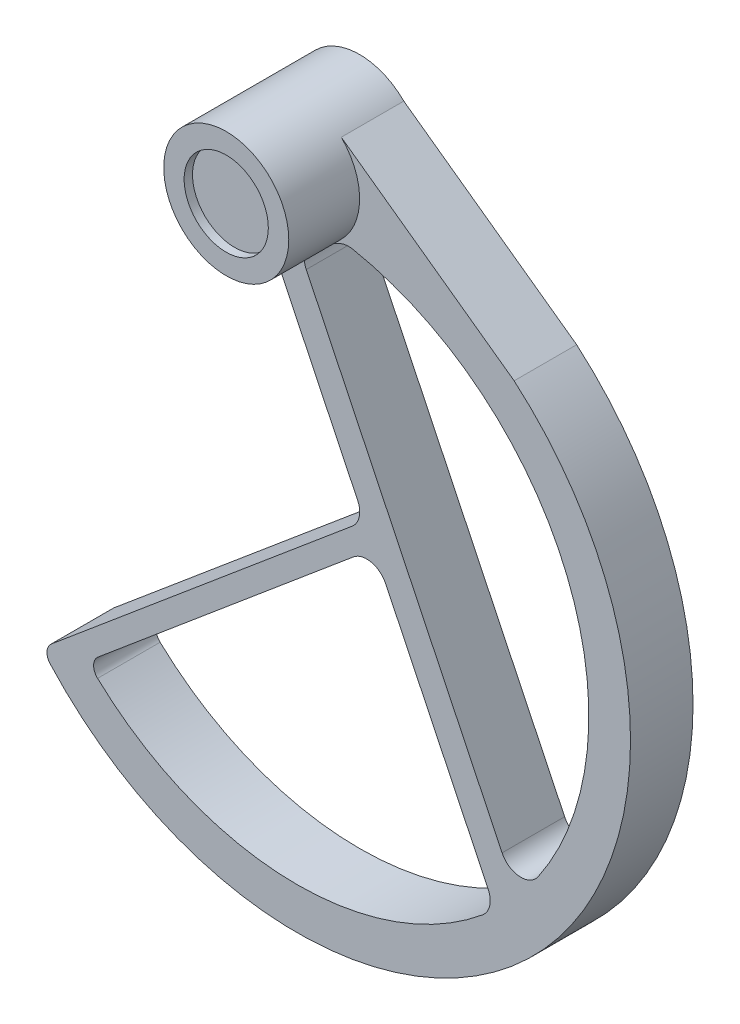
SolidWorks part; units mm, degrees
material "ABS"
ref_plane "正面" through (0, 0, 0) normal (0, 0, 1) x (1, 0, 0)
ref_plane "平面" through (0, 0, 0) normal (0, 1, 0) x (1, 0, 0)
ref_plane "右側面" through (0, 0, 0) normal (1, 0, 0) x (0, 0, -1)
sketch "ｽｹｯﾁ4" plane through (0, 0, 0) normal (0, 0, 1) x (1, 0, 0)
  line L0 (0, 0.7897) -> (0, 0)
  line L1 (-53.6231, -124.9951) -> (-58.9406, -129.4571)
  line L3 (-10.6066, -10.6066) -> (14.5363, -62.8896)
  line L4 (-53.6231, -124.9951) -> (13.2442, -68.8868)
  line L5 (21.2324, -76.8138) -> (45.8448, -127.9938)
  line L6 (10.6066, 10.6066) -> (52.0762, -19.2705)
  line L7 (-58.0696, -135.2532) -> (-57.9498, -135.1527)
  line L8 (-47.7477, -126.5866) -> (13.5112, -75.1515)
  arc A1 (-59.2335, -133.7716) -> (52.0762, -19.2705) centre (0, -80) ccw
  arc A2 (-47.8702, -131.073) -> (44.5187, -134.0193) centre (0, -80) ccw
  arc A3 (10.6066, 10.6066) -> (-10.6066, -10.6066) centre (0, 0) ccw
  arc A4 (-59.2335, -133.7716) -> (-58.9406, -129.4571) centre (-57.0123, -131.7552) cw
  arc A5 (-47.8702, -131.073) -> (-47.7477, -126.5866) centre (-45.8186, -128.8841) cw
  arc A6 (13.5112, -75.1515) -> (21.2324, -76.8138) centre (16.7264, -78.9807) cw
  arc A7 (13.2442, -68.8868) -> (14.5363, -62.8896) centre (10.0302, -65.0566) ccw
  arc A8 (45.8448, -127.9938) -> (44.5187, -134.0193) centre (41.3388, -130.1608) cw
  point P18 (-61.2836, -131.423)
  point P21 (-50.2744, -128.7081)
  point P24 (18.4421, -71.0114)
  dimension "D3" = 140
  dimension "D4" = 30
  dimension "D5" = 5
  dimension "D6" = 3
  dimension "D7" = 3
  dimension "D8" = 5
  dimension "D9" = 5
  dimension "D10" = 5
  dimension "D2" = 5
extrude "ﾎﾞｽ - 押し出し1" add sketch "ｽｹｯﾁ4" along normal blind 15 contours A7 L4 L1 A4 A1 L6 A3 L3 L5 A8 A2 A5 L8 A6 region at (29.7837, -70.5076, 0)
sketch "ｽｹｯﾁ6" plane through (0, 0, 15) normal (0, 0, 1) x (1, 0, 0)
  line L6 (49.1896, -118.7973) -> (2.2018, -21.089)
  line L7 (6.4834, -13.4819) -> (4.5408, -14.416)
  line L8 (6.4834, -13.4819) -> (10.2197, -11.6851)
  arc A0 (57.8261, -119.448) -> (13.3394, -11.2828) centre (0, -80) ccw
  arc A1 (2.2018, -21.089) -> (4.5408, -14.416) centre (6.7078, -18.9221) cw
  arc A2 (13.3394, -11.2828) -> (10.2197, -11.6851) centre (12.3866, -16.1911) ccw
  arc A3 (57.8261, -119.448) -> (49.1896, -118.7973) centre (53.6956, -116.6303) cw
  point P7 (0.0348, -16.583)
  point P14 (52.6925, -126.0814)
  dimension "D3" = 121.502
  dimension "D4" = 70
  dimension "D1" = 5
  dimension "D2" = 5
  dimension "D5" = 5
  dimension "D6" = 90
extrude "ｶｯﾄ - 押し出し1" cut sketch "ｽｹｯﾁ6" against normal blind 15
sketch "ｽｹｯﾁ9" plane through (0, 0, 15) normal (0, 0, 1) x (1, 0, 0)
  circle A0 centre (0, 0) radius 15
extrude "ﾎﾞｽ - 押し出し2" add sketch "ｽｹｯﾁ9" along normal blind 17
sketch "ｽｹｯﾁ10" plane through (0, 0, 32) normal (0, 0, 1) x (1, 0, 0)
  circle A0 centre (0, 0) radius 10.1
extrude "ｶｯﾄ - 押し出し4" cut sketch "ｽｹｯﾁ10" against normal blind 2
